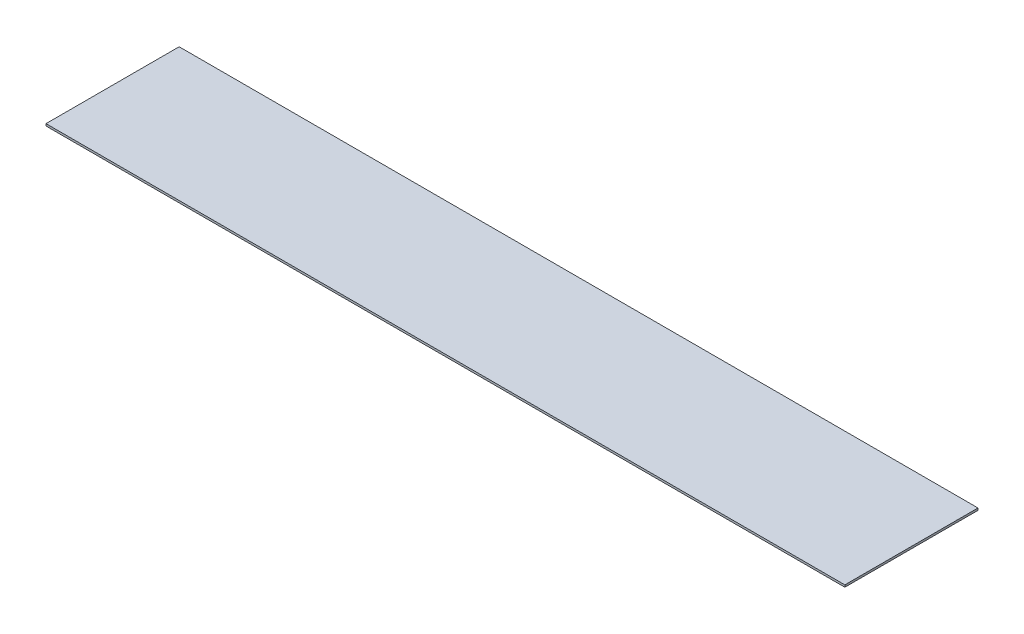
SolidWorks part; units mm, degrees
material "Nylon 101"
ref_plane "Front Plane" through (0, 0, 0) normal (0, 0, 1) x (1, 0, 0)
ref_plane "Top Plane" through (0, 0, 0) normal (0, 1, 0) x (1, 0, 0)
ref_plane "Right Plane" through (0, 0, 0) normal (1, 0, 0) x (0, 0, -1)
sketch "Sketch1" plane through (0, 0, 0) normal (0, -1, 0) x (1, 0, 0)
  line L2 (0, 0) -> (609.6, 0)
  line L3 (0, 0) -> (0, 101.6)
  line L4 (0, 101.6) -> (609.6, 101.6)
  line L5 (609.6, 0) -> (609.6, 101.6)
  point P4 (0, 0)
  point P5 (24.7622, 82.6324)
  point P8 (0, 0)
  point P9 (0, 0)
  dimension "D2" = 609.6
  dimension "D1" = 101.6
extrude "Boss-Extrude1" add sketch "Sketch1" along normal blind 1.5875
